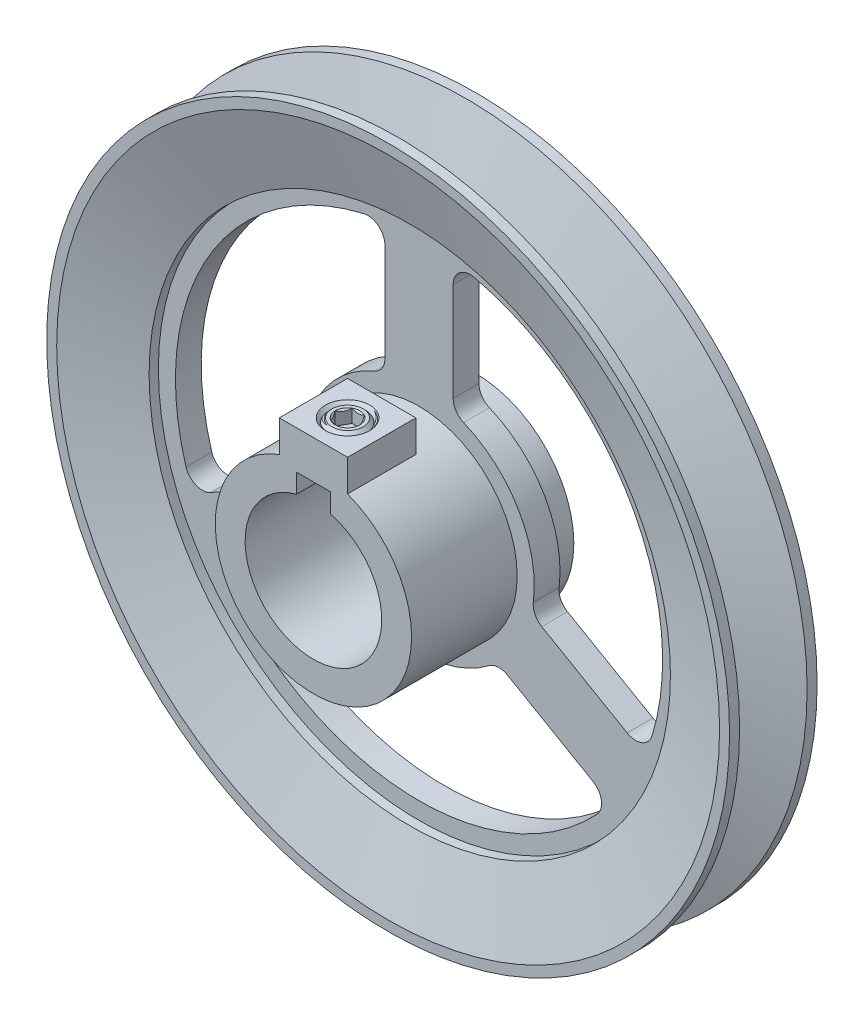
SolidWorks part; units mm, degrees
ref_plane "Front Plane" through (0, 0, 0) normal (0, 0, 1) x (1, 0, 0)
ref_plane "Top Plane" through (0, 0, 0) normal (0, 1, 0) x (1, 0, 0)
ref_plane "Right Plane" through (0, 0, 0) normal (1, 0, 0) x (0, 0, -1)
sketch "Sketch1" plane through (0, 0, 0) normal (1, 0, 0) x (0, 0, -1)
  line L0 (-22.0345, 0) -> (8.1407, 0) construction
  line L1 (-6.2793, 63.5) -> (6.2793, 63.5) construction
  line L2 (6.2793, 63.5) -> (8.1407, 63.5)
  line L5 (-8.1407, 63.5) -> (6.2793, 63.5) construction
  line L7 (-22.0345, 18.2562) -> (-22.0345, -18.2562) construction
  line L10 (-8.1407, 61.6386) -> (-4.1164, 48.4757)
  line L13 (-6.2793, 63.5) -> (-2.3965, 50.8)
  line L14 (-2.3965, 50.8) -> (2.3965, 50.8)
  line L15 (2.3965, 50.8) -> (6.2793, 63.5)
  line L16 (8.1407, 12.7) -> (-22.0345, 12.7) construction
  line L17 (0, 63.5) -> (0, 0) construction
  line L18 (-6.2793, 63.5) -> (-8.1407, 63.5)
  line L20 (-22.0345, 0) -> (-22.0345, 12.7) construction
  line L22 (5.3086, 60.325) -> (-5.3086, 60.325) construction
  line L23 (8.1407, 63.5) -> (8.1407, 0) construction
  line L24 (8.1407, 61.6386) -> (4.1164, 48.4757)
  line L26 (-22.0345, 18.2562) -> (-7.747, 18.2562)
  line L27 (-7.747, 18.2562) -> (8.1407, 18.2562) construction
  line L28 (-4.1164, 48.4757) -> (4.1164, 48.4757) construction
  line L29 (-2.3965, 48.4757) -> (-2.3965, 18.2562)
  line L31 (-22.0345, 18.2562) -> (-22.0345, 0)
  line L32 (-8.1407, 61.6386) -> (-8.1407, 63.5)
  line L33 (8.1407, 63.5) -> (8.1407, 61.6386)
  line L34 (-22.0345, 0) -> (8.1407, 0)
  line L35 (8.1407, 0) -> (8.1407, 18.2562)
  line L36 (2.3965, 18.2562) -> (2.3965, 48.4757)
  line L37 (-2.3965, 18.2562) -> (2.3965, 18.2562) construction
  line L38 (-2.3965, 50.8) -> (-4.6192, 50.1204) construction
  line L39 (-7.747, 18.2562) -> (-2.3965, 18.2562)
  line L40 (8.1407, 18.2562) -> (2.3965, 18.2562)
  line L41 (-2.3965, 50.8) -> (-2.3965, 48.4757) construction
  line L42 (-7.747, 18.2562) -> (-7.747, 0) construction
  line L43 (-4.1164, 48.4757) -> (-2.3965, 48.4757)
  line L44 (4.1164, 48.4757) -> (2.3965, 48.4757)
  point P6 (0, 18.2562)
  point P16 (0, 50.8)
  point P25 (-7.747, 0)
  point P38 (0, 48.4757)
revolve "Revolve1" add sketch "Sketch1" angle 360 about L0
sketch "Sketch2" plane through (0, -7.9375, -8.1407) normal (0, 0, 1) x (0, 1, 0)
  line L2 (71.4375, 0) -> (7.9375, 0) construction
  line L3 (7.9375, 0) -> (-23.8125, -54.9926) construction
  line L6 (-7.0806, -38.7121) -> (2.0928, -22.8233)
  line L9 (30.6254, -6.35) -> (48.9722, -6.35)
  arc A0 (5.2418, -21.261) -> (27.698, -8.296) centre (7.9375, 0) ccw
  arc A1 (-5.2556, -43.337) -> (52.065, -10.2429) centre (7.9375, 0) ccw
  circle A2 centre (7.9375, 0) radius 63.5 construction
  arc A3 (-5.2556, -43.337) -> (-7.0806, -38.7121) centre (-4.331, -40.2996) cw
  arc A4 (52.065, -10.2429) -> (48.9722, -6.35) centre (48.9722, -9.525) ccw
  arc A5 (30.6254, -6.35) -> (27.698, -8.296) centre (30.6254, -9.525) ccw
  arc A6 (2.0928, -22.8233) -> (5.2418, -21.261) centre (4.8424, -24.4108) cw
  circle A7 centre (7.9375, 0) radius 48.4757 construction
  circle A8 centre (7.9375, 0) radius 18.2562 construction
  dimension "D1" = 3.175
  dimension "D2" = 12.7
  dimension "D3" = 12.7
  dimension "D4" = 120
  dimension "D5" = 3.175
  dimension "D6" = 3.175
extrude "Cut-Extrude1" cut sketch "Sketch2" along normal up to surface (16.2814 mm away) up to face at (61.6386, 0, 8.1407)
pattern_circular "CirPattern1" count 3 over 360 about axis through (0, 0, 0) along (0, 0, 1) of "Cut-Extrude1"
sketch "Sketch3" plane through (0, 0, -8.1407) normal (0, 0, -1) x (-1, 0, 0)
  circle A0 centre (0, 0) radius 12.7
  circle A1 centre (0, 0) radius 60.325 construction
  point P4 (0, 12.7)
extrude "Cut-Extrude2" cut sketch "Sketch3" against normal up to vertex (30.1752 mm away) up to point (0, 0, 22.0345)
sketch "Sketch4" plane through (0, 0, -8.1407) normal (0, 0, -1) x (-1, 0, 0)
  line L0 (3.175, 12.7) -> (-3.175, 12.7) construction
  line L1 (3.175, 15.875) -> (-3.175, 15.875)
  line L2 (3.175, 15.875) -> (3.175, 9.525)
  line L3 (3.175, 9.525) -> (-3.175, 9.525)
  line L4 (-3.175, 15.875) -> (-3.175, 9.525)
  dimension "Keyway Wd." = 6.35
  dimension "Keyway Dp." = 3.175
extrude "Cut-Extrude3" cut sketch "Sketch4" against normal up to vertex (30.1752 mm away) up to point (0, 0, 22.0345)
ref_plane "Plane1" through (0, 18.2562, 0) normal (0, 1, 0) x (-1, 0, 0)
sketch "Sketch5" plane through (0, 18.2562, 0) normal (0, 1, 0) x (-1, 0, 0)
  line L0 (0, 22.0345) -> (0, 0) construction
  line L1 (6.35, 9.3345) -> (-6.35, 9.3345)
  line L2 (6.35, 9.3345) -> (6.35, 22.0345)
  line L3 (6.35, 22.0345) -> (-6.35, 22.0345)
  line L4 (-6.35, 9.3345) -> (-6.35, 22.0345)
  line L5 (18.2562, 22.0345) -> (-18.2562, 22.0345) construction
  dimension "D1" = 12.7
extrude "Boss-Extrude1" add sketch "Sketch5" against normal up to surface (5.9024 mm away) from offset 4.7625 up to face at (18.2562, 0, 22.0345)
sketch "Sketch6" plane through (0, 23.0187, 0) normal (0, 1, 0) x (-1, 0, 0)
  line L0 (0, 9.3345) -> (0, 22.0345) construction
  line L1 (6.35, 22.0345) -> (-6.35, 22.0345) construction
  line L2 (-6.35, 9.3345) -> (6.35, 9.3345) construction
  line L7 (0, 19.6532) -> (0, 18.2421) construction
  circle A0 centre (0, 15.6845) radius 3.9688 construction
  circle A1 centre (0, 15.6845) radius 3.0868
  dimension "D3" = 0.8819
extrude "Cut-Extrude4" cut sketch "Sketch6" against normal up to vertex (23.0188 mm away) up to point (0, 0, 22.0345)
sketch "Sketch7" plane through (0, 23.0187, 0) normal (0, 1, 0) x (-1, 0, 0)
  circle A0 centre (0, 15.6845) radius 3.9688 construction
  circle A1 centre (0, 15.6845) radius 3.9688
  point P3 (0, 19.6532)
curve "Helix/Spiral1" pitch 1.4111 height 19.6674 radius 3.9688 centre (0, 23.0187, 15.6845) axis (0, -1, 0) start towards (0, 0, 1)
sketch "Sketch8" plane through (0, 0, 0) normal (1, 0, 0) x (0, 0, -1)
  line L0 (-18.5839, 24.4299) -> (-18.5839, 23.0187) construction
  line L1 (-18.5839, 23.0187) -> (-19.806, 23.7243) construction
  line L2 (-19.806, 23.7243) -> (-18.5839, 24.4299) construction
  line L3 (-18.5839, 23.0187) -> (-19.6532, 23.0187) construction
  line L4 (-19.6532, 23.0187) -> (-19.6532, 23.6361) construction
  line L5 (-19.6532, 23.6361) -> (-19.6532, 23.8125) construction
  line L6 (-18.7367, 23.1069) -> (-18.7367, 24.3417) construction
  line L7 (-19.806, 23.7243) -> (-19.6532, 23.7243) construction
  line L8 (-18.7367, 23.7243) -> (-18.5839, 23.7243) construction
  line L9 (-18.6603, 24.3858) -> (-18.6603, 23.0628)
  line L10 (-18.6603, 23.0628) -> (-19.6532, 23.6361)
  line L11 (-19.6532, 23.6361) -> (-19.6532, 23.8125)
  line L12 (-19.6532, 23.8125) -> (-18.6603, 24.3858)
  point P16 (-18.6603, 23.7243)
  dimension "D1" = 1.4111
  dimension "D2" = 0.1764
sweep "Cut-Sweep1" cut profiles "Sketch8" path "Helix/Spiral1" align with end faces yes
sketch "Sketch9" plane through (0, 23.0187, 0) normal (0, 1, 0) x (-1, 0, 0)
  circle A0 centre (0, 15.6845) radius 4.1215
extrude "Cut-Extrude5" cut sketch "Sketch9" against normal through all draft 45
sketch "Sketch10" plane through (0, 0, 0) normal (1, 0, 0) x (0, 0, -1)
  line L0 (-15.6845, 23.0187) -> (-15.6845, 13.4937) construction
  line L1 (-19.6532, 14.5631) -> (-19.6532, 21.9494)
  line L2 (-15.6845, 23.0187) -> (-19.6532, 23.0187) construction
  line L3 (-15.6845, 23.0187) -> (-15.6845, 13.4937)
  line L4 (-15.6845, 13.4937) -> (-19.6532, 13.4937) construction
  line L5 (-19.6532, 23.0187) -> (-19.6532, 13.4937) construction
  line L6 (-18.5839, 23.0187) -> (-19.6532, 21.9494)
  line L7 (-19.6532, 14.5631) -> (-18.5839, 13.4937)
  line L8 (-18.5839, 23.0187) -> (-15.6845, 23.0187)
  line L9 (-18.5839, 13.4937) -> (-15.6845, 13.4937)
  line L10 (-9.3345, 23.0187) -> (-22.0345, 23.0187) construction
  line L11 (-18.5839, 23.0187) -> (-19.6532, 23.0187) construction
  line L12 (-19.6532, 23.0187) -> (-19.6532, 21.9494) construction
revolve "Revolve3" add sketch "Sketch10" angle 360 about L0
sketch "Sketch11" plane through (0, 23.0187, 0) normal (0, 1, 0) x (-1, 0, 0)
  circle A1 centre (0, 15.6845) radius 3.9688
  circle A2 centre (0, 15.6845) radius 3.9688
  dimension "D1" = 0
curve "Helix/Spiral2" pitch 1.4111 height 10.9361 turns 7.75
sketch "Sketch12" plane through (0, 0, 0) normal (1, 0, 0) x (0, 0, -1)
  line L0 (-19.7296, 23.6802) -> (-19.7296, 22.3573)
  line L1 (-19.7296, 23.7243) -> (-19.7296, 23.6802) construction
  line L2 (-19.806, 23.7243) -> (-19.6532, 23.7243) construction
  line L3 (-18.5839, 23.0187) -> (-19.806, 23.7243) construction
  line L4 (-19.7296, 23.6802) -> (-18.7367, 23.1069)
  line L5 (-18.7367, 23.1069) -> (-18.7367, 22.9306)
  line L6 (-18.7367, 22.9306) -> (-19.7296, 22.3573)
  line L7 (-19.806, 23.7243) -> (-18.5839, 23.0187) construction
  line L8 (-18.5839, 23.0187) -> (-19.806, 22.3132) construction
  line L9 (-19.806, 22.3132) -> (-19.806, 23.7243) construction
sweep "Cut-Sweep2" cut profiles "Sketch12" path "Helix/Spiral2" align with end faces yes
sketch "Sketch13" plane through (0, 23.0187, 0) normal (0, 1, 0) x (1, 0, 0)
  line L1 (2.2914, -15.6845) -> (1.1457, -13.7001)
  line L2 (1.1457, -13.7001) -> (-1.1457, -13.7001)
  line L3 (-1.1457, -13.7001) -> (-2.2914, -15.6845)
  line L4 (-2.2914, -15.6845) -> (-1.1457, -17.6689)
  line L5 (-1.1457, -17.6689) -> (1.1457, -17.6689)
  line L6 (1.1457, -17.6689) -> (2.2914, -15.6845)
  circle A0 centre (0, -15.6845) radius 1.9844 construction
  dimension "D1" = 3.9688
extrude "Cut-Extrude6" cut sketch "Sketch13" against normal blind 2.4805
sketch "Sketch14" plane through (0, 23.0187, 0) normal (0, 1, 0) x (1, 0, 0)
  circle A0 centre (0, -15.6845) radius 2.2914
extrude "Cut-Extrude7" cut sketch "Sketch14" against normal through all draft 45
equation "\"D3@Sketch6\" = \"Screw Pitch@Sketch6\" * 5 / 8"
equation "\"D4@Helix/Spiral1\" = \"Screw Pitch@Sketch6\""
equation "\"D3@Helix/Spiral1\" = \"D4@Helix/Spiral1\" + ( \"Hub Dia.@Sketch1\" / 2 ) "
equation "\"D1@Sketch8\" = \"D4@Helix/Spiral1\""
equation "\"D2@Sketch8\" = \"D1@Sketch8\" / 8"
equation "\"D4@Helix/Spiral2\" = \"D4@Helix/Spiral1\""
equation "\"D3@Helix/Spiral2\" = \"D4@Helix/Spiral2\" + \"Screw Length@Sketch10\""
equation "\"D1@Sketch13\" = \"Screw OD@Sketch6\" / 2"
equation "\"D1@Cut-Extrude6\" = \"D1@Sketch13\" * 5 / 8"
equation "\"D4@Sketch2\" = \"D3@CirPattern1\" / \"Spokes@CirPattern1\""
